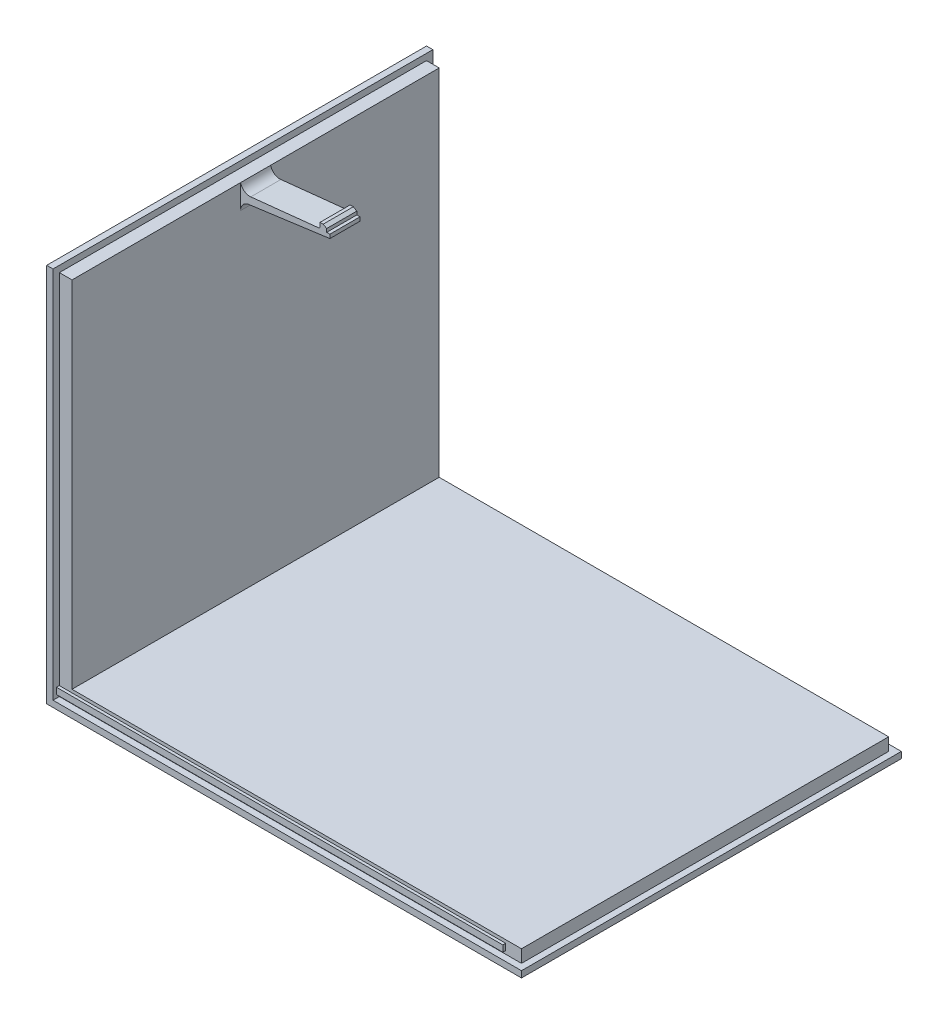
SolidWorks part; units mm, degrees
other "Markup1"
sketch "Sketch5" plane through (-105, 0, 60.5) normal (-0.0451, -0.9984, 0.0353) x (-0.7444, 0.01, -0.6676)
other "Markup2"
sketch "Sketch6" plane through (97, 11, -60) normal (0.0014, 0.7787, -0.6274) x (0.9996, 0.0165, 0.0227)
ref_plane "Front Plane" through (0, 0, 0) normal (0, 0, 1) x (1, 0, 0)
ref_plane "Top Plane" through (0, 0, 0) normal (0, 1, 0) x (1, 0, 0)
ref_plane "Right Plane" through (0, 0, 0) normal (1, 0, 0) x (0, 0, -1)
sketch "Sketch1" plane through (0, 0, 0) normal (0, 1, 0) x (1, 0, 0)
  line L1 (-75, 60) -> (75, 60)
  line L2 (-75, 60) -> (-75, -60)
  line L3 (-75, -60) -> (75, -60)
  line L4 (75, 60) -> (75, -60)
  point P4 (0, 60)
  point P5 (-75, 0)
  dimension "D1" = 120
  dimension "D2" = 150
extrude "Top" add sketch "Sketch1" along normal blind 2
sketch "Sketch2" plane through (0, 2, 0) normal (0, 1, 0) x (1, 0, 0)
  line L1 (-73, -58) -> (73, -58)
  line L2 (-73, -58) -> (-73, 58)
  line L3 (-73, 58) -> (73, 58)
  line L4 (73, -58) -> (73, 58)
  point P4 (0, 58)
  point P7 (73, 0)
  dimension "D1" = 116
  dimension "D2" = 146
extrude "Bottom" add sketch "Sketch2" along normal blind 4
sketch "Sketch8" plane through (0, 2, 0) normal (0, 1, 0) x (1, 0, 0)
  line L0 (-75, -60) -> (75, -60) construction
  line L1 (-75, 60) -> (-73, 60)
  line L2 (-75, 60) -> (-75, -60)
  line L3 (-75, -60) -> (-73, -60)
  line L4 (-73, 60) -> (-73, -60)
  dimension "D1" = 2
extrude "Boss-Extrude2" add sketch "Sketch8" along normal blind 118
sketch "Sketch10" plane through (-73, 0, 0) normal (1, 0, 0) x (0, 0, -1)
  line L1 (-58, 6) -> (58, 6)
  line L2 (-58, 6) -> (-58, 118)
  line L3 (-58, 118) -> (58, 118)
  line L4 (58, 6) -> (58, 118)
  dimension "D1" = 112
  dimension "D2" = 116
extrude "Boss-Extrude3" add sketch "Sketch10" along normal blind 4
sketch "Sketch11" plane through (-73, 0, 0) normal (1, 0, 0) x (0, 0, -1)
  line L0 (-58, 118) -> (-58, 2) construction
  line L1 (-58, 3) -> (-58.9, 3)
  line L2 (-58, 3) -> (-58, 5)
  line L3 (-58, 5) -> (-58.9, 5)
  line L4 (-58.9, 3) -> (-58.9, 5)
  line L6 (-58, 6) -> (-58, 2) construction
  line L7 (0, 0) -> (0, 41.6534) construction
  line L8 (58.9, 3) -> (58.9, 5)
  line L9 (58, 5) -> (58.9, 5)
  line L10 (58, 3) -> (58, 5)
  line L11 (58, 3) -> (58.9, 3)
  point P10 (-58, 4)
  point P11 (-58, 4)
  dimension "D1" = 2
  dimension "D2" = 0.9
extrude "Boss-Extrude4" add sketch "Sketch11" along normal blind 141
sketch "Sketch7" plane through (0, 0, 0) normal (0, 0, 1) x (1, 0, 0)
  line L1 (-69, 115.3724) -> (-69, 112.9724)
  line L17 (-69, 112.9724) -> (-40.7801, 116.8)
  line L18 (-41.7801, 119.06) -> (-42.8814, 119.6959)
  line L19 (-42.8814, 119.6959) -> (-43.8814, 119.6959)
  line L20 (-43.8814, 119.6959) -> (-44, 118)
  line L21 (-44, 118) -> (-69, 115.3724)
  line L22 (-41.7801, 118) -> (-41.7801, 119.06)
  line L23 (-41.7801, 118) -> (-40.7801, 118)
  line L24 (-40.7801, 118) -> (-40.7801, 116.8)
  line L25 (-73, 120) -> (-38.2157, 120) construction
  line L26 (-69, 118) -> (-37.8788, 118) construction
  point P55 (-7.5, 67.5)
extrude "Boss-Extrude1" add sketch "Sketch7" along normal mid plane 9.5
fillet "Fillet1" radius 3 2 edges at (-69, 115.3724, 0) (-69, 112.9724, 0)
